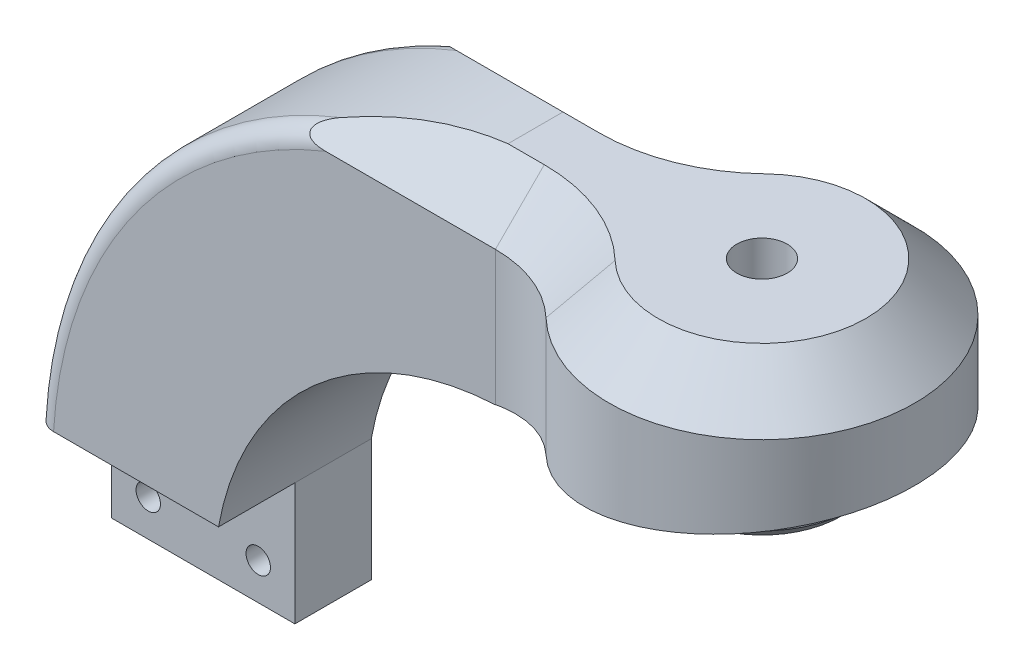
SolidWorks part; units mm, degrees
material "ABS"
ref_plane "Front Plane" through (0, 0, 0) normal (0, 0, 1) x (1, 0, 0)
ref_plane "Top Plane" through (0, 0, 0) normal (0, 1, 0) x (1, 0, 0)
ref_plane "Right Plane" through (0, 0, 0) normal (1, 0, 0) x (0, 0, -1)
sketch "Sketch1" plane through (0, 0, 0) normal (0, 0, 1) x (1, 0, 0)
  line L0 (69.3749, 90) -> (120, 90)
  line L1 (0, 0) -> (30, 0)
  line L2 (0, 0) -> (0, 20)
  line L3 (20, 90) -> (30, 90)
  line L4 (30, 0) -> (30, 20)
  line L5 (20, 90) -> (30, 90)
  line L7 (76.2846, 60) -> (120, 60)
  line L8 (120, 90) -> (120, 60)
  arc A1 (30, 20) -> (79.2135, 60) centre (77.7491, 11.5271) cw
  arc A2 (0, 20) -> (78.8823, 90) centre (74.1286, 15.9111) cw
  dimension "D4" = 20
  dimension "D5" = 20
  dimension "D1" = 30
  dimension "D2" = 30
  dimension "D3" = 90
extrude "Boss-Extrude1" add sketch "Sketch1" along normal blind 25 contours L2 L1 L4 L7 L8 L5 L3 region at (51.6447, 55.6367, 0)
sketch "Sketch3" plane through (0, 90, 0) normal (0, 1, 0) x (1, 0, 0)
  line L0 (120, -12.5) -> (92.8851, -12.5) construction
  line L1 (120, -25) -> (120, 0) construction
  line L2 (69.3749, 0) -> (69.3749, -25)
  line L3 (69.3749, -25) -> (75.3178, -25)
  line L4 (69.3749, -25) -> (120, -25) construction
  line L5 (69.3749, 0) -> (75.3178, 0)
  line L6 (69.3749, 0) -> (120, 0) construction
  arc A0 (89.151, -30.5556) -> (89.151, 5.5556) centre (106.4426, -12.5) ccw
  arc A1 (75.3178, -25) -> (89.151, -30.5556) centre (75.3178, -45) cw
  arc A2 (75.3178, 0) -> (89.151, 5.5556) centre (75.3178, 20) ccw
  point P17 (84.7919, -25)
  point P20 (84.7919, 0)
  dimension "D1" = 50
  dimension "D2" = 20
extrude "Boss-Extrude3" add sketch "Sketch3" against normal up to surface (30 mm away) up to face at (99.6068, 60, 12.5)
ref_axis "Axis1" through (106.4426, 60, 12.5) along (0, 1, 0)
sketch "Sketch4" plane through (0, 0, 0) normal (1, 0, 0) x (0, 0, -1)
  line L0 (-25, 0) -> (0, 0) construction
  line L1 (-12.5, 0) -> (-42.5, 0)
  line L2 (-12.5, 0) -> (-12.5, 20)
  line L3 (-12.5, 20) -> (-42.5, 20)
  line L4 (-42.5, 0) -> (-42.5, 20)
  dimension "D1" = 30
  dimension "D2" = 20
extrude "Cut-Extrude1" cut sketch "Sketch4" along normal blind 49
sketch "Sketch5" plane through (0, 0, 12.5) normal (0, 0, 1) x (1, 0, 0)
  line L0 (30, 14) -> (0, 14) construction
  line L1 (30, 20) -> (30, 0) construction
  line L2 (0, 20) -> (0, 0) construction
  line L3 (30, 20) -> (0, 20) construction
  line L4 (30, 6) -> (0, 6) construction
  line L6 (30, 0) -> (0, 0) construction
  line L7 (0, 0) -> (0, 20) construction
  line L8 (30, 0) -> (30, 20) construction
  circle A0 centre (24, 6) radius 2
  circle A1 centre (6, 6) radius 2
  circle A2 centre (15, 14) radius 2
  dimension "D2" = 4
  dimension "D3" = 4
  dimension "D4" = 4
  dimension "D1" = 6
  dimension "D5" = 15
  dimension "D6" = 6
  dimension "D7" = 6
  dimension "D8" = 6
extrude "Cut-Extrude2" cut sketch "Sketch5" against normal blind 49
sketch "Sketch6" plane through (0, 0, 0) normal (0, 0, 1) x (1, 0, 0)
  line L0 (75.3178, 60) -> (136.8515, 71.3075)
  line L1 (136.8515, 71.3075) -> (136.8515, 40.5377)
  line L2 (136.8515, 40.5377) -> (75.3178, 40.5377)
  line L3 (75.3178, 40.5377) -> (75.3178, 60)
extrude "Cut-Extrude3" cut sketch "Sketch6" against normal mid plane 78
sketch "Sketch7" plane through (0, 90, 0) normal (0, 1, 0) x (1, 0, 0)
  circle A0 centre (106.4426, -12.5) radius 4.125
  dimension "D1" = 8.25
extrude "Cut-Extrude4" cut sketch "Sketch7" against normal blind 78
sketch "Sketch8" plane through (0, 90, 0) normal (0, 1, 0) x (1, 0, 0)
  circle A0 centre (106.4426, -12.5) radius 4.125
  circle A1 centre (106.4426, -12.5) radius 15
  dimension "D1" = 30
extrude "Boss-Extrude4" add sketch "Sketch8" against normal blind 30
sketch "Sketch9" plane through (0, 60, 0) normal (0, -1, 0) x (1, 0, 0)
  line L0 (106.4426, 12.5) -> (126.7329, 12.5) construction
  line L2 (114.2368, 12.5) -> (110.3397, 19.25)
  line L3 (110.3397, 19.25) -> (102.5454, 19.25)
  line L4 (102.5454, 19.25) -> (98.6483, 12.5)
  line L5 (98.6483, 12.5) -> (102.5454, 5.75)
  line L6 (102.5454, 5.75) -> (110.3397, 5.75)
  line L7 (110.3397, 5.75) -> (114.2368, 12.5)
  circle A0 centre (106.4426, 12.5) radius 6.75 construction
  dimension "D1" = 13.5
extrude "Cut-Extrude5" cut sketch "Sketch9" against normal blind 7
chamfer "Chamfer1" distance 8 angle 45 5 edges at (72.3464, 90, 25) (72.3464, 90, 0) (82.7714, 90, 26.4408) (82.7714, 90, -1.4408) (131.4426, 90, 12.5)
fillet "Fillet1" radius 3 2 edges at (11.8839, 56.3754, 0) (11.8839, 56.3754, 25)
chamfer "Chamfer2" distance 2 angle 45 1 edges at (106.4426, 60, 27.5)
